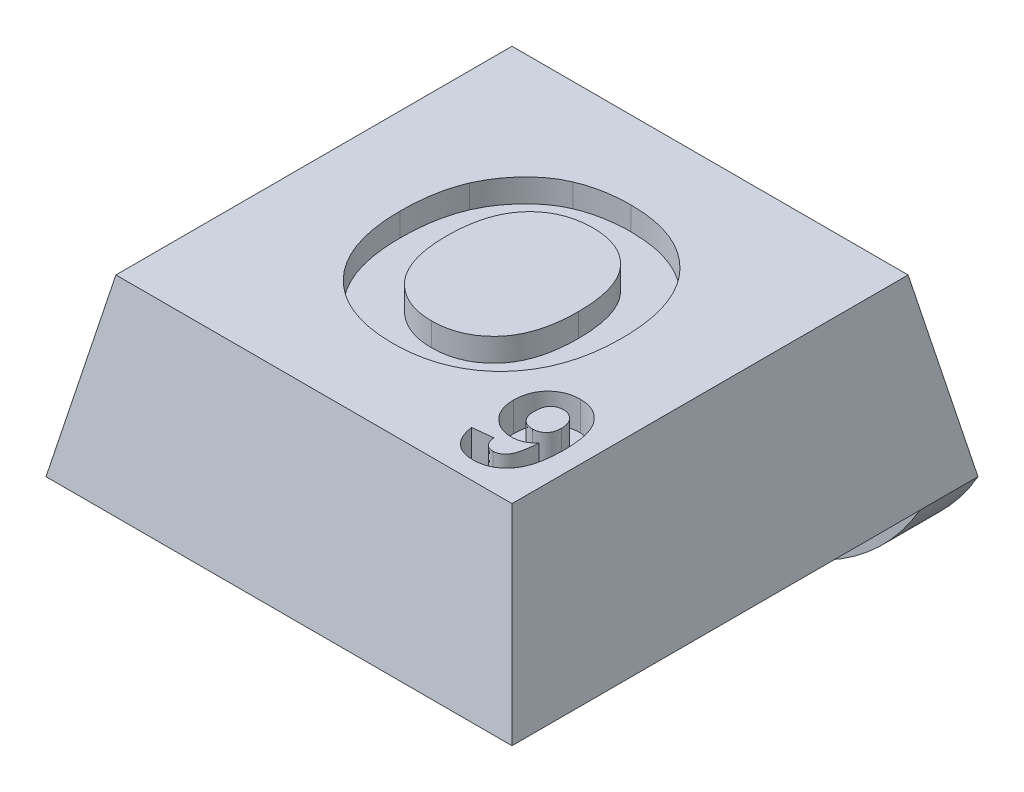
SolidWorks part; units mm, degrees
ref_plane "Front Plane" through (0, 0, 0) normal (0, 0, 1) x (1, 0, 0)
ref_plane "Top Plane" through (0, 0, 0) normal (0, 1, 0) x (1, 0, 0)
ref_plane "Right Plane" through (0, 0, 0) normal (1, 0, 0) x (0, 0, -1)
sketch "Sketch1" plane through (0, 0, 0) normal (0, 1, 0) x (1, 0, 0)
  line L1 (0, 0) -> (8, 0)
  line L2 (0, 0) -> (0, 8)
  line L3 (0, 8) -> (8, 8)
  line L4 (8, 0) -> (8, 8)
  dimension "D1" = 8
  dimension "D2" = 8
extrude "Boss-Extrude1" add sketch "Sketch1" along normal blind 3
sketch "Sketch2" plane through (0, 0, 0) normal (0, 0, 1) x (1, 0, 0)
  line L0 (0, 0) -> (0.6, 3)
  line L1 (0, 3) -> (8, 3) construction
  line L2 (0.6, 3) -> (0, 3)
  line L3 (0, 3) -> (0, 0)
  line L4 (8, 0) -> (7.4, 3)
  line L5 (7.4, 3) -> (8, 3)
  line L6 (8, 3) -> (8, 0)
  dimension "D1" = 0.6
  dimension "D2" = 0.6
extrude "Cut-Extrude1" cut sketch "Sketch2" against normal through all both and the other way through all
sketch "Sketch3" plane through (0, 0, 0) normal (1, 0, 0) x (0, 0, -1)
  line L0 (0, 0) -> (0.6, 3)
  line L1 (8, 3) -> (0, 3) construction
  line L2 (0.6, 3) -> (0, 3)
  line L3 (0, 3) -> (0, 0)
  line L4 (8, 3) -> (7.4, 3)
  line L5 (7.4, 3) -> (8, 0)
  line L6 (8, 3) -> (8, 0)
  dimension "D1" = 0.6
  dimension "D2" = 0.6
extrude "Cut-Extrude2" cut sketch "Sketch3" along normal blind 11
sketch "Sketch4" plane through (0, 0, 0) normal (0, -1, 0) x (1, 0, 0)
  line L0 (8, 0) -> (8, -8) construction
  line L3 (0, 0) -> (8, 0) construction
  circle A0 centre (4, -3.75) radius 1.75
  dimension "D1" = 3.5
  dimension "D2" = 4
  dimension "D3" = 3.75
extrude "Cut-Extrude3" cut sketch "Sketch4" against normal blind 0.4
sketch "Sketch5" plane through (0, 0, 0) normal (0, -1, 0) x (1, 0, 0)
  line L0 (8, 0) -> (8, -8) construction
  line L1 (0, -8) -> (8, -8)
  line L2 (0, -8) -> (0, -7)
  line L3 (0, -7) -> (8, -7)
  line L4 (8, -8) -> (8, -7)
  dimension "D1" = 1
extrude "Boss-Extrude2" add sketch "Sketch5" along normal blind 2
fillet "Fillet1" radius 4 2 edges at (8, -2, -7.5) (0, -2, -7.5)
sketch "Sketch6" plane through (0, 3, 0) normal (0, 1, 0) x (1, 0, 0)
  text T0 "O" font "Arial" height 4
extrude "Cut-Extrude4" cut sketch "Sketch6" against normal blind 0.4
sketch "Sketch7" plane through (0, 3, 0) normal (0, 1, 0) x (1, 0, 0)
  text T0 "9" font "Arial" height 1.8
extrude "Cut-Extrude5" cut sketch "Sketch7" against normal blind 0.5
